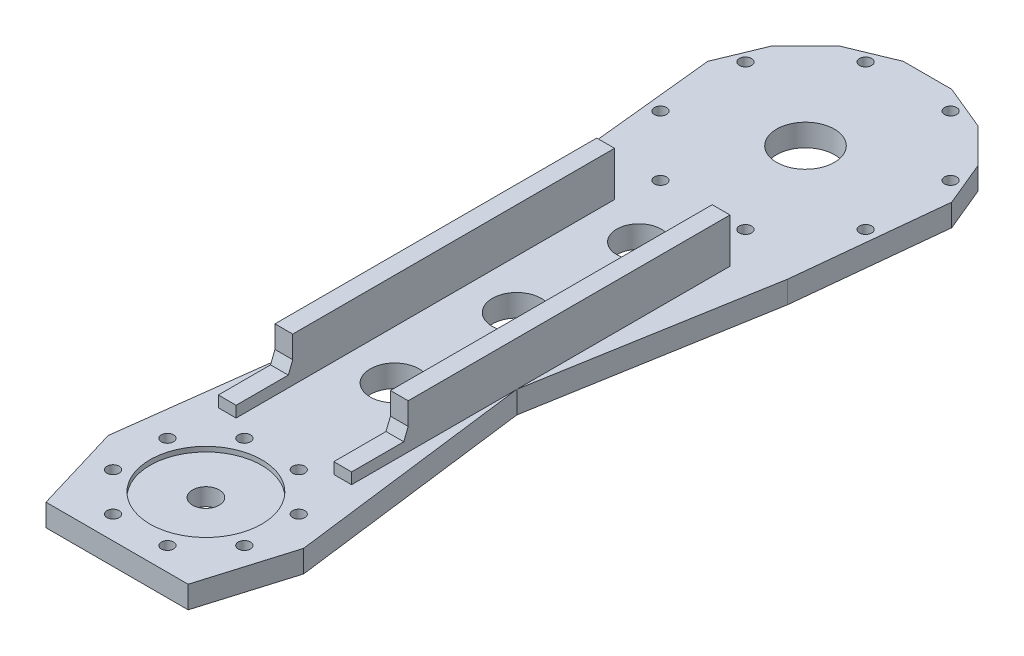
SolidWorks part; units mm, degrees
ref_plane "Front Plane" through (0, 0, 0) normal (0, 0, 1) x (1, 0, 0)
ref_plane "Top Plane" through (0, 0, 0) normal (0, 1, 0) x (1, 0, 0)
ref_plane "Right Plane" through (0, 0, 0) normal (1, 0, 0) x (0, 0, -1)
ref_plane "PL_Thigh_Plate_base" through (0, -46, 0) normal (0, 1, 0) x (1, 0, 0)
sketch "SK_Thigh_Plate" plane through (0, -46, 0) normal (0, 1, 0) x (1, 0, 0)
  line L0 (-32, -40) -> (32, -40)
  line L1 (32, -40) -> (44, 0)
  line L2 (44, 0) -> (30, 110)
  line L3 (30, 110) -> (48, 214)
  line L4 (48, 214) -> (54.924, 280.9251)
  line L5 (54.924, 280.9251) -> (46.5623, 301.1119)
  line L6 (46.5623, 301.1119) -> (31.1119, 316.5623)
  line L7 (31.1119, 316.5623) -> (10.9251, 324.924)
  line L8 (10.9251, 324.924) -> (-10.9251, 324.924)
  line L9 (-10.9251, 324.924) -> (-31.1119, 316.5623)
  line L10 (-31.1119, 316.5623) -> (-46.5623, 301.1119)
  line L11 (-46.5623, 301.1119) -> (-54.924, 280.9251)
  line L12 (-54.924, 280.9251) -> (-48, 214)
  line L13 (-48, 214) -> (-30, 110)
  line L14 (-30, 110) -> (-44, 0)
  line L15 (-44, 0) -> (-32, -40)
  circle A0 centre (29.5641, 12.2459) radius 2.75
  circle A1 centre (12.2459, 29.5641) radius 2.75
  circle A2 centre (-12.2459, 29.5641) radius 2.75
  circle A3 centre (-29.5641, 12.2459) radius 2.75
  circle A4 centre (-29.5641, -12.2459) radius 2.75
  circle A5 centre (-12.2459, -29.5641) radius 2.75
  circle A6 centre (12.2459, -29.5641) radius 2.75
  circle A7 centre (29.5641, -12.2459) radius 2.75
  circle A8 centre (46.194, 289.1342) radius 2.75
  circle A9 centre (19.1342, 316.194) radius 2.75
  circle A10 centre (-19.1342, 316.194) radius 2.75
  circle A11 centre (-46.194, 289.1342) radius 2.75
  circle A12 centre (-46.194, 250.8658) radius 2.75
  circle A13 centre (-19.1342, 223.806) radius 2.75
  circle A14 centre (19.1342, 223.806) radius 2.75
  circle A15 centre (46.194, 250.8658) radius 2.75
  circle A16 centre (0, 0) radius 6
  circle A17 centre (0, 270) radius 13
  circle A18 centre (0, 85) radius 11
  circle A19 centre (0, 140) radius 11
  circle A20 centre (0, 195) radius 10
  dimension "D31_SK_Thigh_Plate" = 5.5
  dimension "D34_SK_Thigh_Plate" = 5.5
  dimension "D37_SK_Thigh_Plate" = 5.5
  dimension "D40_SK_Thigh_Plate" = 5.5
  dimension "D43_SK_Thigh_Plate" = 5.5
  dimension "D46_SK_Thigh_Plate" = 5.5
  dimension "D49_SK_Thigh_Plate" = 5.5
  dimension "D52_SK_Thigh_Plate" = 5.5
  dimension "D55_SK_Thigh_Plate" = 5.5
  dimension "D58_SK_Thigh_Plate" = 5.5
  dimension "D61_SK_Thigh_Plate" = 5.5
  dimension "D64_SK_Thigh_Plate" = 5.5
  dimension "D67_SK_Thigh_Plate" = 5.5
  dimension "D70_SK_Thigh_Plate" = 5.5
  dimension "D73_SK_Thigh_Plate" = 5.5
  dimension "D76_SK_Thigh_Plate" = 5.5
  dimension "D79_SK_Thigh_Plate" = 12
  dimension "D80_SK_Thigh_Plate" = 26
  dimension "D82_SK_Thigh_Plate" = 22
  dimension "D84_SK_Thigh_Plate" = 22
  dimension "D86_SK_Thigh_Plate" = 20
  dimension "P1" = 32
  dimension "P2" = 40
  dimension "P3" = 32
  dimension "P4" = 40
  dimension "P5" = 44
  dimension "P6" = 30
  dimension "P7" = 110
  dimension "P8" = 48
  dimension "P9" = 214
  dimension "P10" = 54.924
  dimension "P11" = 280.9251
  dimension "P12" = 46.5623
  dimension "P13" = 301.1119
  dimension "P14" = 31.1119
  dimension "P15" = 316.5623
  dimension "P16" = 10.9251
  dimension "P17" = 324.924
  dimension "P18" = 10.9251
  dimension "P19" = 324.924
  dimension "P20" = 31.1119
  dimension "P21" = 316.5623
  dimension "P22" = 46.5623
  dimension "P23" = 301.1119
  dimension "P24" = 54.924
  dimension "P25" = 280.9251
  dimension "P26" = 48
  dimension "P27" = 214
  dimension "P28" = 30
  dimension "P29" = 110
  dimension "P30" = 44
  dimension "P32" = 29.5641
  dimension "P33" = 12.2459
  dimension "P35" = 12.2459
  dimension "P36" = 29.5641
  dimension "P38" = 12.2459
  dimension "P39" = 29.5641
  dimension "P41" = 29.5641
  dimension "P42" = 12.2459
  dimension "P44" = 29.5641
  dimension "P45" = 12.2459
  dimension "P47" = 12.2459
  dimension "P48" = 29.5641
  dimension "P50" = 12.2459
  dimension "P51" = 29.5641
  dimension "P53" = 29.5641
  dimension "P54" = 12.2459
  dimension "P56" = 46.194
  dimension "P57" = 289.1342
  dimension "P59" = 19.1342
  dimension "P60" = 316.194
  dimension "P62" = 19.1342
  dimension "P63" = 316.194
  dimension "P65" = 46.194
  dimension "P66" = 289.1342
  dimension "P68" = 46.194
  dimension "P69" = 250.8658
  dimension "P71" = 19.1342
  dimension "P72" = 223.806
  dimension "P74" = 19.1342
  dimension "P75" = 223.806
  dimension "P77" = 46.194
  dimension "P78" = 250.8658
  dimension "P81" = 270
  dimension "P83" = 85
  dimension "P85" = 140
  dimension "P87" = 195
extrude "Thigh_Plate" add sketch "SK_Thigh_Plate" along normal blind 10
ref_plane "PL_Pitch_Pilot_Recess_base" through (0, -36, 0) normal (0, 1, 0) x (1, 0, 0)
sketch "SK_Pitch_Pilot_Recess" plane through (0, -36, 0) normal (0, 1, 0) x (1, 0, 0)
  circle A0 centre (0, 0) radius 25.15
  dimension "D1_SK_Pitch_Pilot_Recess" = 50.3
extrude "Pitch_Pilot_Recess" cut sketch "SK_Pitch_Pilot_Recess" against normal blind 2.2
ref_plane "PL_Front_Flange_base" through (22, 0, 0) normal (1, 0, 0) x (0, 0, -1)
sketch "SK_Front_Flange" plane through (22, 0, 0) normal (1, 0, 0) x (0, 0, -1)
  line L0 (35.5977, -31) -> (35.5977, -36)
  line L1 (35.5977, -36) -> (206, -36)
  line L2 (206, -36) -> (206, -16)
  line L3 (206, -16) -> (61.0999, -16)
  line L4 (61.0999, -16) -> (61.0999, -26)
  line L5 (61.0999, -26) -> (59.0999, -31)
  line L6 (59.0999, -31) -> (35.5977, -31)
  dimension "P1" = 35.5977
  dimension "P2" = 31
  dimension "P3" = 35.5977
  dimension "P4" = 36
  dimension "P5" = 206
  dimension "P6" = 36
  dimension "P7" = 206
  dimension "P8" = 16
  dimension "P9" = 61.0999
  dimension "P10" = 16
  dimension "P11" = 61.0999
  dimension "P12" = 26
  dimension "P13" = 59.0999
  dimension "P14" = 31
extrude "Front_Flange" add sketch "SK_Front_Flange" along normal blind 8
ref_plane "PL_Back_Flange_base" through (-30, 0, 0) normal (1, 0, 0) x (0, 0, -1)
sketch "SK_Back_Flange" plane through (-30, 0, 0) normal (1, 0, 0) x (0, 0, -1)
  line L0 (35.5977, -31) -> (35.5977, -36)
  line L1 (35.5977, -36) -> (206, -36)
  line L2 (206, -36) -> (206, -16)
  line L3 (206, -16) -> (61.0999, -16)
  line L4 (61.0999, -16) -> (61.0999, -26)
  line L5 (61.0999, -26) -> (59.0999, -31)
  line L6 (59.0999, -31) -> (35.5977, -31)
  dimension "P1" = 35.5977
  dimension "P2" = 31
  dimension "P3" = 35.5977
  dimension "P4" = 36
  dimension "P5" = 206
  dimension "P6" = 36
  dimension "P7" = 206
  dimension "P8" = 16
  dimension "P9" = 61.0999
  dimension "P10" = 16
  dimension "P11" = 61.0999
  dimension "P12" = 26
  dimension "P13" = 59.0999
  dimension "P14" = 31
extrude "Back_Flange" add sketch "SK_Back_Flange" along normal blind 8
ref_axis "AX_PitchY" through (0, -14.5, 0) along (0, -1, 0)
ref_plane "PL_PitchRef" through (0, 0, 0) normal (-0.6428, 0, 0.766) x (0, -1, 0)
equation "\"Thigh_length\" = 270"
equation "\"Thigh_plate_t\" = 10"
equation "\"Flange_end_z\" = -206"
equation "\"Flange_deep_start_z\" = -61.0999"
equation "\"Flange_shallow_start_z\" = -35.5977"
